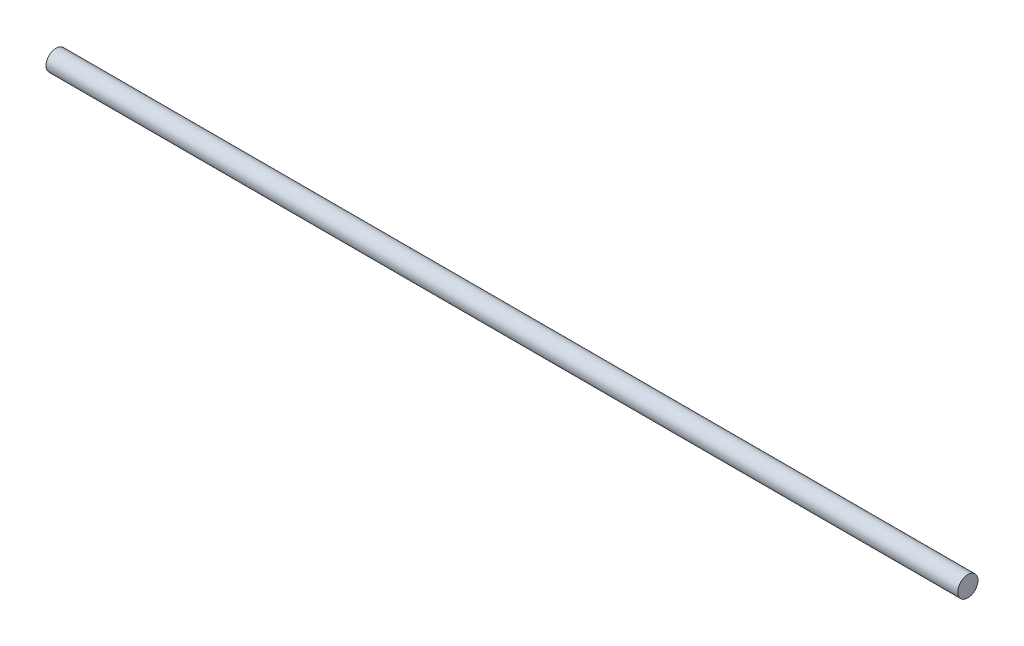
SolidWorks part; units mm, degrees
ref_plane "Front Plane" through (0, 0, 0) normal (0, 0, 1) x (1, 0, 0)
ref_plane "Top Plane" through (0, 0, 0) normal (0, 1, 0) x (1, 0, 0)
ref_plane "Right Plane" through (0, 0, 0) normal (1, 0, 0) x (0, 0, -1)
sketch "Sketch1" plane through (0, 0, 0) normal (1, 0, 0) x (0, 0, -1)
  circle A0 centre (0, 0) radius 3.81
  dimension "D1" = 7.62
extrude "Boss-Extrude1" add sketch "Sketch1" along normal blind 342.9
ref_plane "Plane1" through (6.35, 0, 0) normal (-1, 0, 0) x (0, 0, 1)
ref_plane "Plane2" through (336.55, 0, 0) normal (1, 0, 0) x (0, 0, -1)
ref_axis "Axis1" through (342.9, 0, 0) along (-1, 0, 0)
ref_point "Point1"
ref_point "Point2"
